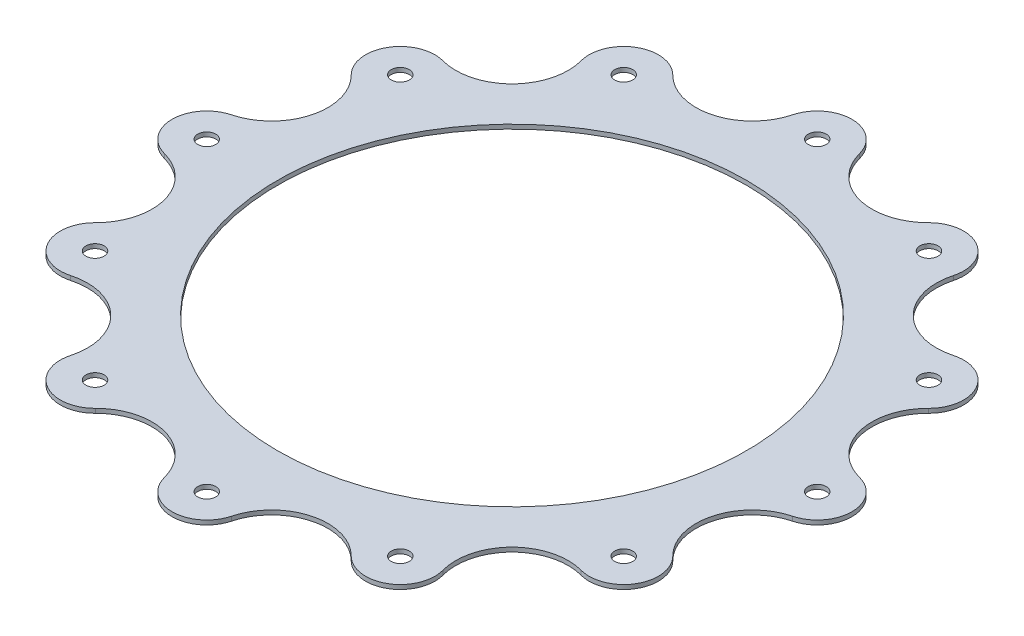
SolidWorks part; units mm, degrees
material "Copper"
ref_plane "Front Plane" through (0, 0, 0) normal (0, 0, 1) x (1, 0, 0)
ref_plane "Top Plane" through (0, 0, 0) normal (0, 1, 0) x (1, 0, 0)
ref_plane "Right Plane" through (0, 0, 0) normal (1, 0, 0) x (0, 0, -1)
sketch "Sketch1" plane through (0, 0, 0) normal (0, 1, 0) x (1, 0, 0)
  circle A7 centre (0, 0) radius 85.8139
  circle A9 centre (0, 0) radius 124.46
  dimension "D1" = 248.92
  dimension "D4" = 171.6278
extrude "Boss-Extrude1" add sketch "Sketch1" along normal blind 1.5875 contours A9 | A7
sketch "Sketch2" plane through (0, 1.5875, 0) normal (0, 1, 0) x (1, 0, 0)
  circle A0 centre (0, 111.76) radius 12.7 construction
  circle A1 centre (0, 111.76) radius 3.302
  circle A2 centre (0, 0) radius 124.46 construction
  dimension "D1" = 6.604
  dimension "D2" = 25.4
extrude "Cut-Extrude1" cut sketch "Sketch2" against normal up to next
pattern_circular "CirPattern1" count 12 over 360 about axis through (0, 1.5875, 0) along (0, -1, 0) of "Cut-Extrude1" reverse direction yes
sketch "Sketch4" plane through (0, 1.5875, 0) normal (0, 1, 0) x (1, 0, 0)
  line L0 (0, 124.46) -> (0, 155.1465)
  line L1 (0, 155.1465) -> (77.5732, 134.3608)
  line L2 (77.5732, 134.3608) -> (62.23, 107.7855)
  circle A0 centre (0, 111.76) radius 12.7 construction
  circle A1 centre (0, 0) radius 124.46 construction
  circle A2 centre (55.88, 96.787) radius 12.7 construction
  circle A3 centre (32.2126, 120.2191) radius 20.6048 construction
  arc A4 (0, 124.46) -> (12.2835, 114.9857) centre (0, 111.76) cw
  arc A5 (62.23, 107.7855) -> (46.855, 105.7223) centre (55.88, 96.787) ccw
  arc A6 (12.2835, 114.9857) -> (46.855, 105.7223) centre (32.2126, 120.2191) ccw
  circle A7 centre (55.88, 96.787) radius 3.302 construction
  dimension "D1" = 25.4
extrude "Cut-Extrude2" cut sketch "Sketch4" against normal up to next
pattern_circular "CirPattern2" count 12 over 360 about axis through (0, 1.5875, 0) along (0, -1, 0) of "Cut-Extrude2" reverse direction yes
equation "\"D_Chamber\"= 6.757"
equation "\"D_Plate\"= 9.5"
